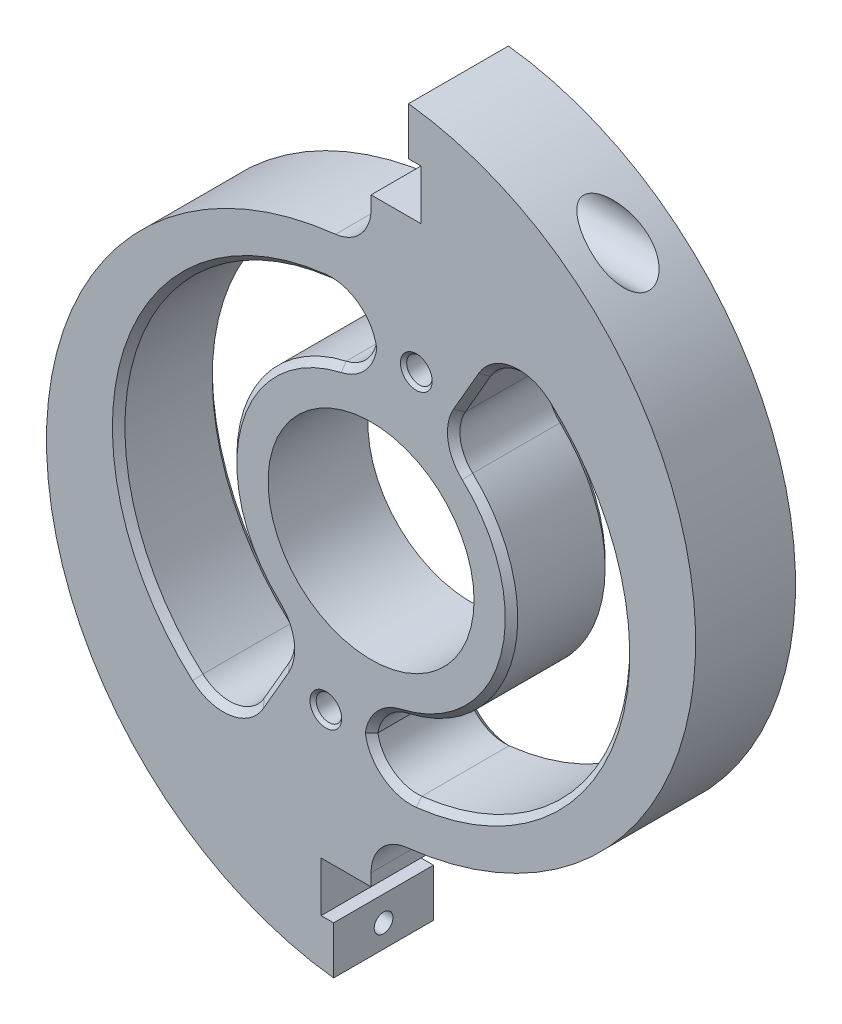
SolidWorks part; units mm, degrees
material "Plain Carbon Steel"
ref_plane "Front Plane" through (0, 0, 0) normal (0, 0, 1) x (1, 0, 0)
ref_plane "Top Plane" through (0, 0, 0) normal (0, 1, 0) x (1, 0, 0)
ref_plane "Right Plane" through (0, 0, 0) normal (1, 0, 0) x (0, 0, -1)
sketch "Sketch1" plane through (0, 0, 0) normal (0, 0, 1) x (1, 0, 0)
  line L0 (0, -203.2) -> (0, -127)
  line L1 (0, 203.2) -> (0, 127)
  line L2 (0, 152.4) -> (0, -228.6) construction
  circle A0 centre (0, 0) radius 203.2 construction
  circle A1 centre (0, 0) radius 52.3875
  arc A2 (0, -127) -> (0, 203.2) centre (0, 38.1) ccw
  arc A3 (0, 127) -> (0, -203.2) centre (0, -38.1) ccw
  dimension "D1" = 406.4
  dimension "D2" = 104.775
  dimension "D3" = 76.2
  dimension "D4" = 76.2
extrude "Boss-Extrude1" add sketch "Sketch1" along normal blind 50.8 contours L1 A3 L0 A2 A1 region at (-159.8637, -38.1, 0)
sketch "Sketch2" plane through (0, 0, 50.8) normal (0, 0, 1) x (1, 0, 0)
  line L0 (0, 103.1875) -> (0, 71.4375)
  line L1 (0, -103.1875) -> (0, -71.4375)
  line L2 (-51.5938, -89.363) -> (-35.7188, -61.8667)
  line L3 (51.5938, 89.363) -> (35.7188, 61.8667)
  arc A0 (0, 71.4375) -> (-35.7188, -61.8667) centre (0, 0) ccw
  circle A1 centre (0, 0) radius 52.3875 construction
  arc A2 (0, 103.1875) -> (-51.5938, -89.363) centre (0, 0) ccw
  circle A3 centre (0, 0) radius 103.1875 construction
  circle A4 centre (0, 0) radius 71.4375 construction
  arc A5 (0, -71.4375) -> (35.7188, 61.8667) centre (0, 0) ccw
  arc A6 (0, -103.1875) -> (51.5938, 89.363) centre (0, 0) ccw
  point P18 (0, 0)
  dimension "D1" = 19.05
  dimension "D3" = 30
  dimension "D4" = 30
  dimension "D2" = 31.75
extrude "Cut-Extrude1" cut sketch "Sketch2" against normal blind 50.8
sketch "Sketch4" plane through (0, 0, 0) normal (0, 0, -1) x (-1, 0, 0)
  line L0 (-51.5938, 89.363) -> (-68.745, 119.0698)
  line L1 (-68.745, 119.0698) -> (50.5485, -87.5527) construction
  line L2 (51.5937, -89.363) -> (68.745, -119.0698)
  line L3 (68.745, -119.0698) -> (-50.5485, 87.5527) construction
  arc A0 (-68.745, 119.0698) -> (0, -103.1875) centre (-9.0982, 15.7586) ccw
  arc A1 (-51.5938, 89.363) -> (0, -103.1875) centre (0, 0) ccw construction
  arc A2 (-51.5938, 89.363) -> (0, -103.1875) centre (0, 0) ccw
  arc A3 (68.745, -119.0698) -> (0, 103.1875) centre (9.0982, -15.7586) ccw
  arc A4 (51.5937, -89.363) -> (0, 103.1875) centre (0, 0) ccw
  point P14 (0, 0)
  dimension "D1" = 2
extrude "Cut-Extrude3" cut sketch "Sketch4" against normal blind 50.8
fillet "Fillet2" radius 20.32 10 edges at (0, -127, 25.4) (68.745, 119.0698, 25.4) (35.7188, 61.8667, 25.4) (0, -71.4375, 25.4) (0, -103.1875, 25.4) (-68.745, -119.0698, 25.4) (-35.7188, -61.8667, 25.4) (0, 127, 25.4) (0, 71.4375, 25.4) (0, 103.1875, 25.4)
chamfer "Chamfer2" distance 3.175 angle 45 28 edges at (5.5785, -75.4939, 0) (69.0033, -18.4894, 0) (42.2459, 64.2918, 0) (51.1352, 88.5688, 0) (71.923, 109.5518, 0) (8.1321, -98.8358, 0) (122.7644, -20.4483, 0) (-8.1321, 98.8358, 0) (-5.5785, 75.4939, 0) (-122.7644, 20.4483, 0) (-69.0033, 18.4894, 0) (-71.923, -109.5518, 0) (-42.2459, -64.2918, 0) (-51.1352, -88.5688, 0) (5.5785, -75.4939, 50.8) (69.0033, -18.4894, 50.8) (42.2459, 64.2918, 50.8) (51.1352, 88.5688, 50.8) (71.923, 109.5518, 50.8) (8.1321, -98.8358, 50.8) (122.7644, -20.4483, 50.8) (-8.1321, 98.8358, 50.8) (-5.5785, 75.4939, 50.8) (-122.7644, 20.4483, 50.8) (-69.0033, 18.4894, 50.8) (-71.923, -109.5518, 50.8) (-42.2459, -64.2918, 50.8) (-51.1352, -88.5688, 50.8)
sketch "Sketch5" plane through (0, 0, 0) normal (0, 0, -1) x (-1, 0, 0)
  line L1 (0, -203.2) -> (25.4, -203.2)
  line L2 (0, -203.2) -> (0, -152.4)
  line L3 (0, -152.4) -> (25.4, -152.4)
  line L4 (25.4, -203.2) -> (25.4, -152.4)
  line L5 (25.4, -177.8) -> (19.05, -177.8)
  line L6 (25.4, -177.8) -> (25.4, -203.2)
  line L7 (25.4, -203.2) -> (19.05, -203.2)
  line L8 (19.05, -177.8) -> (19.05, -203.2)
  line M23 (0, -146.2032) -> (0, -203.2)
  arc M24 (0, -203.2) -> (18.0932, 126.0056) centre (0, -38.1) ccw
  dimension "D1" = 50.8
  dimension "D2" = 25.4
  dimension "D3" = 6.35
extrude "Cut-Extrude4" cut sketch "Sketch5" against normal through all contours L8 L5 L4 L3 M23 M24 region at (-11.3209, -175.8182, 0)
sketch "Sketch6" plane through (-25.4, 0, 0) normal (1, 0, 0) x (0, 0, -1)
  line L0 (0, -168.275) -> (-50.8, -168.275)
  line L3 (-50.8, -177.8) -> (-50.8, -152.4) construction
  line L4 (0, -152.4) -> (0, -177.8) construction
  line L5 (-50.8, -152.4) -> (0, -152.4) construction
  circle A0 centre (-25.4, -168.275) radius 6.35
  dimension "D1" = 12.7
  dimension "D2" = 15.875
extrude "Cut-Extrude5" cut sketch "Sketch6" against normal through all contours A0
sketch "Sketch7" plane through (-25.4, 0, 0) normal (1, 0, 0) x (0, 0, -1)
  line L1 (-35.5184, -172.586) -> (-26.7258, -179.1933)
  line L2 (-26.7258, -179.1933) -> (-16.6073, -174.8823)
  line L3 (-16.6073, -174.8823) -> (-15.2816, -163.964)
  line L4 (-15.2816, -163.964) -> (-24.0742, -157.3567)
  line L5 (-24.0742, -157.3567) -> (-34.1927, -161.6677)
  line L6 (-34.1927, -161.6677) -> (-35.5184, -172.586)
  circle A1 centre (-25.4, -168.275) radius 9.525 construction
  circle A2 centre (-25.4, -168.275) radius 12.7
  dimension "D1" = 19.05
  dimension "D2" = 25.4
extrude "Cut-Extrude6" cut sketch "Sketch7" against normal through all from offset 38.1 contours A2 offset against normal yes
sketch "Sketch9" plane through (-19.05, 0, 0) normal (1, 0, 0) x (0, 0, -1)
  line L0 (-25.4, -177.8) -> (-25.3853, -190.5)
  line L1 (-50.8, -177.8) -> (0, -177.8) construction
  circle A0 centre (-25.3853, -190.5) radius 4.7625
  dimension "D1" = 9.525
  dimension "D2" = 12.7
extrude "Cut-Extrude8" cut sketch "Sketch9" against normal blind 9.525 contours A0
pattern_circular "CirPattern1" count 2 over 360 about axis through (0, 0, 50.8) along (0, 0, 1) of "Cut-Extrude8", "Cut-Extrude4", "Cut-Extrude5", "Cut-Extrude6"
sketch "Sketch10" plane through (0, 0, 50.8) normal (0, 0, 1) x (1, 0, 0)
  line L0 (0, 88.9) -> (0, 0)
  line L1 (0, 0) -> (23.009, 85.8708)
  line L2 (0, 0) -> (-23.009, -85.8708)
  circle A0 centre (0, 0) radius 88.9
  circle A1 centre (23.009, 85.8708) radius 6.477
  circle A2 centre (-23.009, -85.8708) radius 6.477
  dimension "D1" = 15
  dimension "D2" = 177.8
  dimension "D3" = 12.954
extrude "Cut-Extrude9" cut sketch "Sketch10" against normal through all contours A1 | A2
chamfer "Chamfer3" distance 1.5875 angle 45 4 edges at (29.486, 85.8708, 0) (-16.532, -85.8708, 0) (-16.532, -85.8708, 50.8) (29.486, 85.8708, 50.8)
